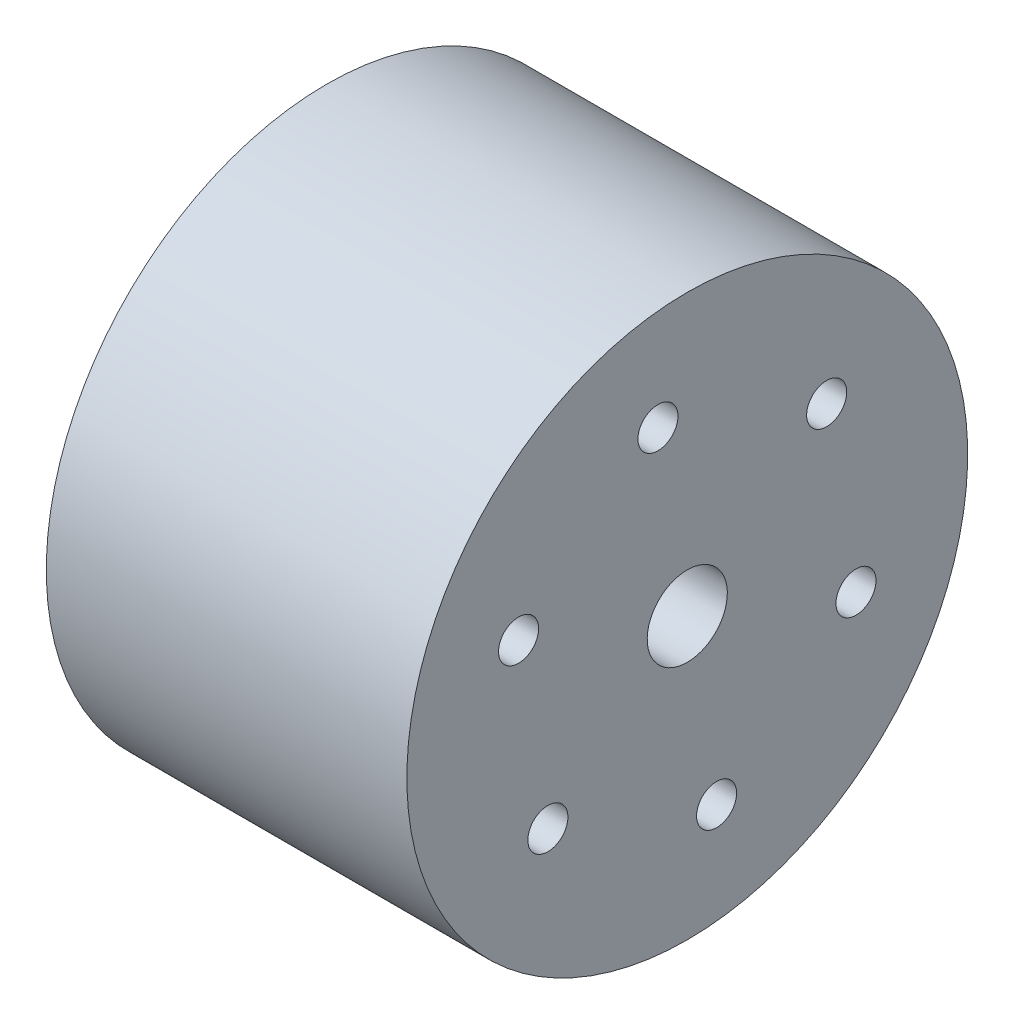
SolidWorks part; units mm, degrees
ref_plane "Front Plane" through (0, 0, 0) normal (0, 0, 1) x (1, 0, 0)
ref_plane "Top Plane" through (0, 0, 0) normal (0, 1, 0) x (1, 0, 0)
ref_plane "Right Plane" through (0, 0, 0) normal (1, 0, 0) x (0, 0, -1)
sketch "Sketch1" plane through (0, 0, 0) normal (0, 0, 1) x (1, 0, 0)
  line L0 (-38.7161, 35) -> (-38.7161, 16)
  line L1 (-38.7161, 16) -> (-33.7161, 16)
  line L2 (-33.7161, 16) -> (-33.7161, 5)
  line L3 (-33.7161, 5) -> (6.2839, 5)
  line L4 (6.2839, 5) -> (6.2839, 35)
  line L5 (6.2839, 35) -> (-38.7161, 35)
  line L6 (-38.7161, -33) -> (-38.7161, 33) construction
  line L9 (0, 0) -> (6.2839, 0) construction
  line L10 (-33.7161, -16) -> (-33.7161, 16) construction
  line L13 (0, 0) -> (-58.1661, 0) construction
  dimension "D1" = 45
  dimension "D2" = 30
  dimension "D3" = 32
revolve "Revolve1" add sketch "Sketch1" angle 360 about L9
sketch "Sketch2" plane through (-38.7161, 0, 0) normal (-1, 0, 0) x (0, 0, 1)
  circle A0 centre (21.0557, 7.9314) radius 2.5
  circle A2 centre (17.3966, -14.2691) radius 2.5
  circle A3 centre (-3.6591, -22.2005) radius 2.5
  circle A4 centre (-21.0557, -7.9314) radius 2.5
  circle A5 centre (-17.3966, 14.2691) radius 2.5
  circle A6 centre (3.6591, 22.2005) radius 2.5
  circle A9 centre (21.0557, 7.9314) radius 2.5 construction
  point P20 (0, 0)
  dimension "D1" = 6
extrude "Cut-Extrude1" cut sketch "Sketch2" against normal up to surface (45 mm away) up to face at (6.2839, -35, 0)
